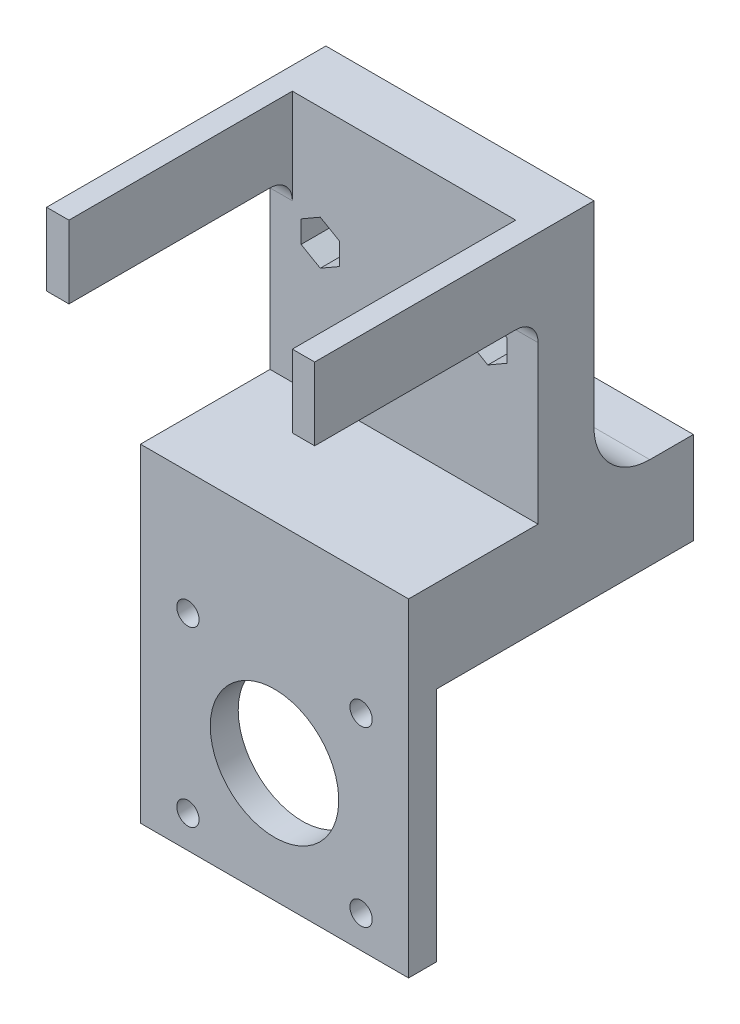
SolidWorks part; units mm, degrees
ref_plane "Front Plane" through (0, 0, 0) normal (0, 0, 1) x (1, 0, 0)
ref_plane "Top Plane" through (0, 0, 0) normal (0, 1, 0) x (1, 0, 0)
ref_plane "Right Plane" through (0, 0, 0) normal (1, 0, 0) x (0, 0, -1)
sketch "Sketch1" plane through (0, 0, 0) normal (0, 0, 1) x (1, 0, 0)
  line L1 (0, 0) -> (48, 0)
  line L2 (0, 0) -> (0, 53)
  line L3 (0, 53) -> (48, 53)
  line L4 (48, 0) -> (48, 53)
  dimension "D1" = 53
  dimension "D2" = 48
extrude "Boss-Extrude1" add sketch "Sketch1" along normal blind 10
sketch "Sketch2" plane through (0, 0, 0) normal (0, 0, -1) x (-1, 0, 0)
  line L0 (0, 53) -> (0, 0) construction
  line L1 (-48, 0) -> (0, 0)
  line L2 (-48, 0) -> (-48, -5.6163)
  line L3 (-48, -5.6163) -> (0, -5.6163)
  line L4 (0, 0) -> (0, -5.6163)
  dimension "D1" = 5.6163
extrude "Boss-Extrude2" add sketch "Sketch2" against normal blind 33.1918
sketch "Sketch4" plane through (0, 0, 10) normal (0, 0, 1) x (1, 0, 0)
  line L1 (0, 53) -> (4, 53)
  line L2 (0, 53) -> (0, 43)
  line L3 (0, 43) -> (4, 43)
  line L4 (4, 53) -> (4, 43)
  line L5 (48, 53) -> (44, 53)
  line L6 (48, 53) -> (48, 43)
  line L7 (48, 43) -> (44, 43)
  line L8 (44, 53) -> (44, 43)
  dimension "D1" = 10
  dimension "D2" = 4
extrude "Boss-Extrude4" add sketch "Sketch4" along normal blind 40
sketch "Sketch5" plane through (0, 0, 10) normal (0, 0, 1) x (1, 0, 0)
  line L0 (48, 0) -> (48, 43) construction
  line L1 (0, 0) -> (48, 0)
  line L2 (0, 0) -> (0, 10.8609)
  line L3 (0, 10.8609) -> (48, 10.8609)
  line L4 (48, 0) -> (48, 10.8609)
  dimension "D1" = 10.8609
extrude "Boss-Extrude5" add sketch "Sketch5" along normal up to surface (23.1918 mm away) up to face at (24, -2.8082, 33.1918)
sketch "Sketch6" plane through (0, -5.6163, 0) normal (0, -1, 0) x (1, 0, 0)
  line L0 (0, 0) -> (0, 28.1918) construction
  line L1 (0, 33.1918) -> (0, 0) construction
  line L2 (48, 33.1918) -> (48, 0) construction
  line L3 (0, 28.1918) -> (48, 28.1918)
  line L4 (0, 28.1918) -> (0, 33.1918)
  line L5 (0, 33.1918) -> (48, 33.1918)
  line L6 (48, 28.1918) -> (48, 33.1918)
  line L8 (48, 33.1918) -> (0, 33.1918) construction
  dimension "D2" = 5
extrude "Boss-Extrude6" add sketch "Sketch6" along normal blind 42.3
sketch "Sketch7" plane through (0, 0, 0) normal (-1, 0, 0) x (0, 0, 1)
  line L0 (33.1918, 10.8609) -> (10, 10.8609) construction
  line L1 (0, -5.6163) -> (-12.8082, -5.6163)
  line L2 (0, -5.6163) -> (0, 10.8609)
  line L3 (0, 10.8609) -> (-12.8082, 10.8609)
  line L4 (-12.8082, -5.6163) -> (-12.8082, 10.8609)
  line L5 (28.1918, -47.9163) -> (28.1918, -5.6163) construction
  dimension "D1" = 41
extrude "Boss-Extrude7" add sketch "Sketch7" against normal up to surface (48 mm away) up to face at (48, 10.6657, 24.2767)
sketch "Sketch8" plane through (0, 0, 28.1918) normal (0, 0, -1) x (-1, 0, 0)
  line L0 (-24, -26.6163) -> (-24, -5.6163) construction
  line L1 (0, -5.6163) -> (-48, -5.6163) construction
  line L3 (-8.5, -42.1163) -> (-39.5, -42.1163) construction
  line L4 (-8.5, -42.1163) -> (-8.5, -11.1163) construction
  line L5 (-8.5, -11.1163) -> (-39.5, -11.1163) construction
  line L6 (-39.5, -42.1163) -> (-39.5, -11.1163) construction
  line L7 (-8.5, -42.1163) -> (-39.5, -11.1163) construction
  line L8 (-8.5, -11.1163) -> (-39.5, -42.1163) construction
  circle A0 centre (-24, -26.6163) radius 11.5
  circle A1 centre (-39.5, -11.1163) radius 2
  circle A2 centre (-39.5, -42.1163) radius 2
  circle A3 centre (-8.5, -11.1163) radius 2
  circle A4 centre (-8.5, -42.1163) radius 2
  dimension "D2" = 23
  dimension "D4" = 4
  dimension "D1" = 21
  dimension "D3" = 31
extrude "Cut-Extrude1" cut sketch "Sketch8" against normal up to next
fillet "Fillet1" radius 10 1 edges at (24, 10.8609, 0)
fillet "Fillet2" radius 4 2 edges at (2, 43, 10) (46, 43, 10)
sketch "Sketch9" plane through (48, 0, 0) normal (1, 0, 0) x (0, 0, -1)
  line L1 (12.8082, 10.8609) -> (17.8082, 10.8609)
  line L2 (12.8082, 10.8609) -> (12.8082, -5.6163)
  line L3 (12.8082, -5.6163) -> (17.8082, -5.6163)
  line L4 (17.8082, 10.8609) -> (17.8082, -5.6163)
  line L5 (-28.1918, -5.6163) -> (12.8082, -5.6163) construction
  dimension "D1" = 5
extrude "Boss-Extrude9" add sketch "Sketch9" against normal up to surface (48 mm away) contours L4 L3 L2 L1 up to face at (0, 13.3569, 15.8852)
sketch "Sketch10" plane through (0, 0, 10) normal (0, 0, 1) x (1, 0, 0)
  line L0 (4, 53) -> (9, 35) construction
  line L1 (9, 35) -> (39, 35) construction
  line L2 (39, 35) -> (44, 53) construction
  line L3 (44, 53) -> (4, 53) construction
  line L4 (44, 53) -> (44, 43) construction
  line L6 (12.429, 36.9797) -> (9, 38.9595)
  line L7 (9, 38.9595) -> (5.571, 36.9797)
  line L8 (5.571, 36.9797) -> (5.571, 33.0203)
  line L9 (5.571, 33.0203) -> (9, 31.0405)
  line L10 (9, 31.0405) -> (12.429, 33.0203)
  line L11 (12.429, 33.0203) -> (12.429, 36.9797)
  line L12 (35.571, 36.9797) -> (35.571, 33.0203)
  line L13 (35.571, 33.0203) -> (39, 31.0405)
  line L14 (39, 31.0405) -> (42.429, 33.0203)
  line L15 (42.429, 33.0203) -> (42.429, 36.9797)
  line L16 (42.429, 36.9797) -> (39, 38.9595)
  line L17 (39, 38.9595) -> (35.571, 36.9797)
  circle A0 centre (9, 35) radius 3.429 construction
  circle A1 centre (39, 35) radius 3.429 construction
  point P3 (0, 0)
  dimension "D1" = 6.858
  dimension "D2" = 30
  dimension "D3" = 18
extrude "Cut-Extrude2" cut sketch "Sketch10" against normal blind 6
sketch "Sketch11" plane through (0, 0, 4) normal (0, 0, 1) x (1, 0, 0)
  circle A0 centre (9, 35) radius 1.9304
  circle A1 centre (39, 35) radius 1.9304
  dimension "D1" = 3.8608
extrude "Cut-Extrude3" cut sketch "Sketch11" against normal blind 6
sketch "Sketch12" plane through (0, 53, 0) normal (0, 1, 0) x (1, 0, 0)
  line L0 (0, 0) -> (0, -50)
  line L1 (0, -50) -> (4, -50)
  line L2 (4, -50) -> (4, -10)
  line L3 (4, -10) -> (44, -10)
  line L4 (44, -10) -> (44, -50)
  line L5 (44, -50) -> (48, -50)
  line L6 (48, -50) -> (48, 0)
  line L7 (48, 0) -> (0, 0)
extrude "Boss-Extrude11" add sketch "Sketch12" along normal blind 3
